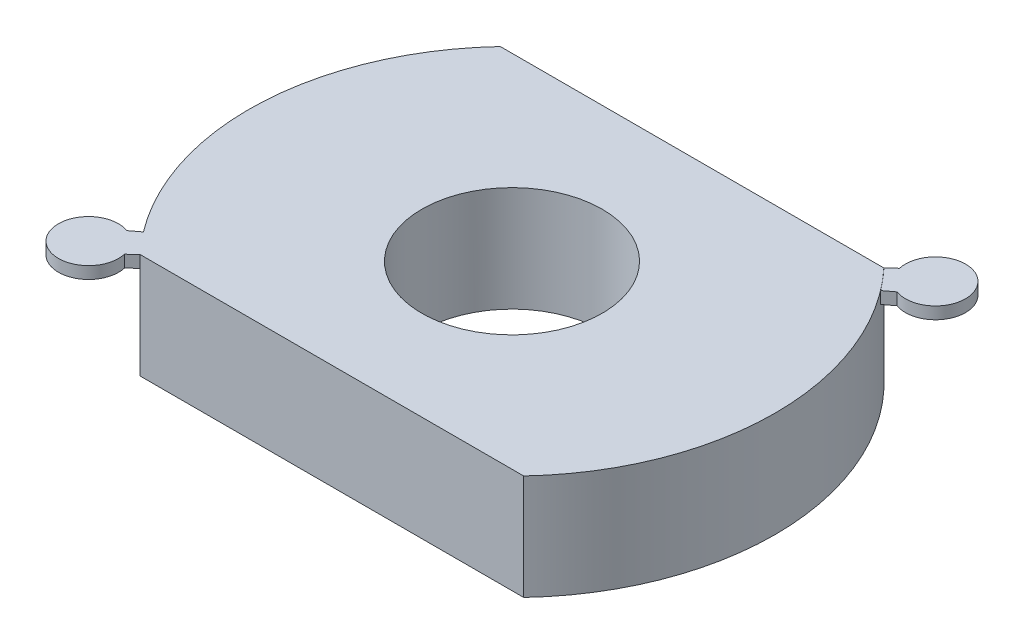
SolidWorks part; units mm, degrees
material "1345 Alloy"
ref_plane "Front Plane" through (0, 0, 0) normal (0, 0, 1) x (1, 0, 0)
ref_plane "Top Plane" through (0, 0, 0) normal (0, 1, 0) x (1, 0, 0)
ref_plane "Right Plane" through (0, 0, 0) normal (1, 0, 0) x (0, 0, -1)
sketch "Sketch1" plane through (0, 0, 0) normal (0, 1, 0) x (1, 0, 0)
  line L0 (-1712.4333, 578.2677) -> (-1658.0172, 559.892) construction
  line L1 (-1682.6566, 611.2885) -> (-1644.8226, 597.5438) construction
  line L2 (-1769.951, 660.0706) -> (-1712.4333, 741.8735) construction
  circle A0 centre (0, 0) radius 1750
  arc A3 (-1712.4333, 578.2677) -> (-1712.4333, 741.8735) centre (-1769.951, 660.0706) cw construction
  arc A4 (-1712.4333, 741.8735) -> (-1682.6566, 611.2885) centre (-1769.951, 660.0706) cw construction
extrude "Boss-Extrude1" add sketch "Sketch1" along normal blind 700
sketch "Sketch9" plane through (0, 0, 0) normal (0, -1, 0) x (1, 0, 0)
  line L1 (-2106.3119, -1198.0599) -> (2106.3119, -1198.0599)
  line L2 (-2106.3119, -1198.0599) -> (-2106.3119, 1198.0599)
  line L3 (-2106.3119, 1198.0599) -> (2106.3119, 1198.0599)
  line L4 (2106.3119, -1198.0599) -> (2106.3119, 1198.0599)
  line L5 (-2106.3119, -1198.0599) -> (2106.3119, 1198.0599) construction
  line L6 (-2106.3119, 1198.0599) -> (2106.3119, -1198.0599) construction
  line L7 (-2636.6179, -2082.9122) -> (2636.6179, -2082.9122)
  line L8 (-2636.6179, -2082.9122) -> (-2636.6179, 2082.9122)
  line L9 (-2636.6179, 2082.9122) -> (2636.6179, 2082.9122)
  line L10 (2636.6179, -2082.9122) -> (2636.6179, 2082.9122)
  line L11 (-2636.6179, -2082.9122) -> (2636.6179, 2082.9122) construction
  line L12 (-2636.6179, 2082.9122) -> (2636.6179, -2082.9122) construction
  point P0 (0, 0)
  point P6 (0, 0)
extrude "Cut-Extrude10" cut sketch "Sketch9" against normal through all both and the other way through all
sketch "Sketch3" plane through (0, 0, 0) normal (0, -1, 0) x (1, 0, 0)
  circle A0 centre (0, 0) radius 600
extrude "Cut-Extrude3" cut sketch "Sketch3" against normal through all both and the other way through all
shell "Shell1" thickness 1.5 removed face at (0, 0, 600)
sketch "Sketch12" plane through (0, 700, 0) normal (0, 1, 0) x (1, 0, 0)
  line L0 (-1275.7204, -1197.9305) -> (-1329.4274, -1248.3625)
  line L1 (-1275.7204, -1197.9305) -> (-1329.4274, -1248.3625)
  line L2 (-1456.8867, -1104.0663) -> (-1394.7434, -1056.9725)
  line L3 (-1212.6439, -1163.1539) -> (-1394.7434, -1056.9725) construction
  line L4 (-1329.4274, -1248.3625) -> (-1275.8583, -1198.0599) construction
  line L5 (1275.5989, -1198.0599) -> (-1275.5989, -1198.0599) construction
  line L6 (-1275.5989, 1198.0599) -> (1275.5989, -1198.0599) construction
  line L7 (0, 0) -> (-1750, 0) construction
  line L13 (0, 0) -> (0, 1750) construction
  line L14 (1212.6439, 1163.1539) -> (1394.7434, 1056.9725) construction
  line L15 (1329.4274, 1248.3625) -> (1275.8583, 1198.0599) construction
  line L16 (1275.7204, 1197.9305) -> (1329.4274, 1248.3625)
  line L17 (1275.7204, 1197.9305) -> (1329.4274, 1248.3625)
  line L18 (1456.8867, 1104.0663) -> (1394.7434, 1056.9725)
  arc A0 (-1275.5989, -1198.0599) -> (-1524.5473, -859.2179) centre (0, 0) cw
  arc A1 (-1275.7204, 1197.9305) -> (-1275.5989, 1198.0599) centre (0, 0) ccw construction
  arc A2 (-1329.4274, -1248.3625) -> (-1456.8867, -1104.0663) centre (-1524.5473, -1292.2737) cw
  arc A3 (-1275.7204, -1197.9305) -> (-1275.5989, -1198.0599) centre (0, 0) cw construction
  arc A4 (1275.8583, 1198.0599) -> (1394.7434, 1056.9725) centre (24.3381, 22.854) cw
  arc A6 (1329.4274, 1248.3625) -> (1456.8867, 1104.0663) centre (1524.5473, 1292.2737) cw
  arc M6 (-1275.5989, 1198.0599) -> (-1275.5989, -1198.0599) centre (0, 0) ccw
extrude "Boss-Extrude2" add sketch "Sketch12" against normal blind 80 contours A2 L0 L2 M6 region at (-1511.5348, 700, 1280.7775)
extrude "Boss-Extrude3" add sketch "Sketch12<6>" against normal blind 80 separate body contours A6 L17 A4 L18 region at (1511.5672, 700, -1280.8004)
sketch "Sketch12<6>" plane through (0, 700, 0) normal (0, 1, 0) x (1, 0, 0) same geometry as "Sketch12"
sketch "Sketch13" plane through (0, 698.5, 0) normal (0, -1, 0) x (-1, 0, 0)
  line L0 (938.2248, -598.28) -> (838.2248, -598.28) construction
  line L1 (938.2248, -598.28) -> (1274.9496, -1196.5599)
  line L2 (838.2248, -598.28) -> (838.2248, -698.28) construction
  line L3 (838.2248, -698.28) -> (1038.2248, -698.28) construction
  line L4 (1038.2248, -698.28) -> (1038.2248, -498.28) construction
  line L5 (938.2248, -598.28) -> (1274.9496, -1196.5599) construction
  line L6 (1274.9496, 1196.5599) -> (938.2248, -598.28) construction
  line L7 (1274.9496, -1196.5599) -> (1274.9496, 1196.5599) construction
  line L8 (1038.2248, -498.28) -> (838.2248, -498.28) construction
  line L9 (838.2248, -498.28) -> (838.2248, -598.28) construction
  line L10 (838.2248, -498.28) -> (838.2248, -698.28)
  line L11 (838.2248, -698.28) -> (1038.2248, -698.28)
  line L12 (1038.2248, -698.28) -> (1038.2248, -498.28)
  line L13 (1038.2248, -498.28) -> (838.2248, -498.28)
  circle A1 centre (938.2248, -598.28) radius 27.5
extrude "Boss-Extrude4" add sketch "Sketch13" along normal blind 50 contours A1 L11 L12 L13 L10 region at (-916.3659, 698.5, 695.4515)
